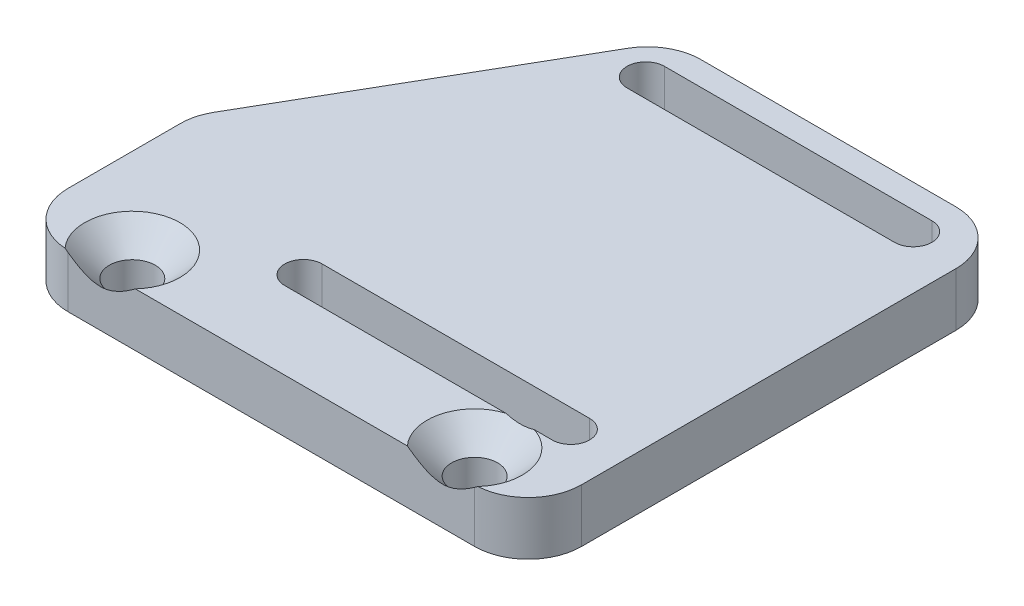
SolidWorks part; units mm, degrees
ref_plane "Front Plane" through (0, 0, 0) normal (0, 0, 1) x (1, 0, 0)
ref_plane "Top Plane" through (0, 0, 0) normal (0, 1, 0) x (1, 0, 0)
ref_plane "Right Plane" through (0, 0, 0) normal (1, 0, 0) x (0, 0, -1)
sketch "Sketch1" plane through (0, 0, 0) normal (0, 1, 0) x (1, 0, 0)
  line L0 (-30, 9) -> (-5, 9) construction
  line L1 (0, 0) -> (-48, 0)
  line L2 (0, 0) -> (0, 45)
  line L3 (0, 45) -> (-48, 45)
  line L4 (-48, 0) -> (-48, 45)
  line L5 (-30, 10.75) -> (-5, 10.75)
  line L6 (-30, 7.25) -> (-5, 7.25)
  line L7 (-30, 41) -> (-5, 41) construction
  line L8 (-30, 42.75) -> (-5, 42.75)
  line L9 (-30, 39.25) -> (-5, 39.25)
  circle A0 centre (-40, 3) radius 2.15
  circle A1 centre (-8, 3) radius 2.15
  arc A2 (-30, 10.75) -> (-30, 7.25) centre (-30, 9) ccw
  arc A3 (-5, 7.25) -> (-5, 10.75) centre (-5, 9) ccw
  arc A4 (-30, 42.75) -> (-30, 39.25) centre (-30, 41) ccw
  arc A5 (-5, 39.25) -> (-5, 42.75) centre (-5, 41) ccw
  point P9 (-17.5, 9)
  point P16 (-17.5, 41)
  point P23 (0, 0)
  point P25 (0, 52.2488)
  dimension "D1" = 4.3
  dimension "D2" = 8
  dimension "D3" = 8
  dimension "D4" = 32
  dimension "D5" = 1.75
  dimension "D8" = 3
  dimension "D10" = 5
  dimension "D6" = 4
  dimension "32" = 32
  dimension "D7" = 6
  dimension "D9" = 25
extrude "Boss-Extrude1" add sketch "Sketch1" along normal blind 5
sketch "Sketch2" plane through (0, 5, 0) normal (0, 1, 0) x (1, 0, 0)
  line L0 (-31.7321, 45) -> (-48, 16.8231)
  line L5 (0, 45) -> (-48, 45) construction
  line L6 (-48, 45) -> (-48, 0) construction
  line L7 (-48, 16.8231) -> (-48, 45)
  line L8 (-48, 45) -> (-31.7321, 45)
  arc A2 (-30, 42.75) -> (-30, 39.25) centre (-30, 41) ccw construction
  dimension "D1" = 60
  dimension "D2" = 3.5
extrude "Cut-Extrude1" cut sketch "Sketch2" against normal through all both and the other way through all
fillet "Fillet1" radius 5 5 edges at (-31.7321, 2.5, -45) (0, 2.5, 0) (-48, 2.5, 0) (-48, 2.5, -16.8231) (0, 2.5, -45)
chamfer "Chamfer1" distance 2.3 angle 45 2 edges at (-8, 5, -0.85) (-40, 5, -0.85)
